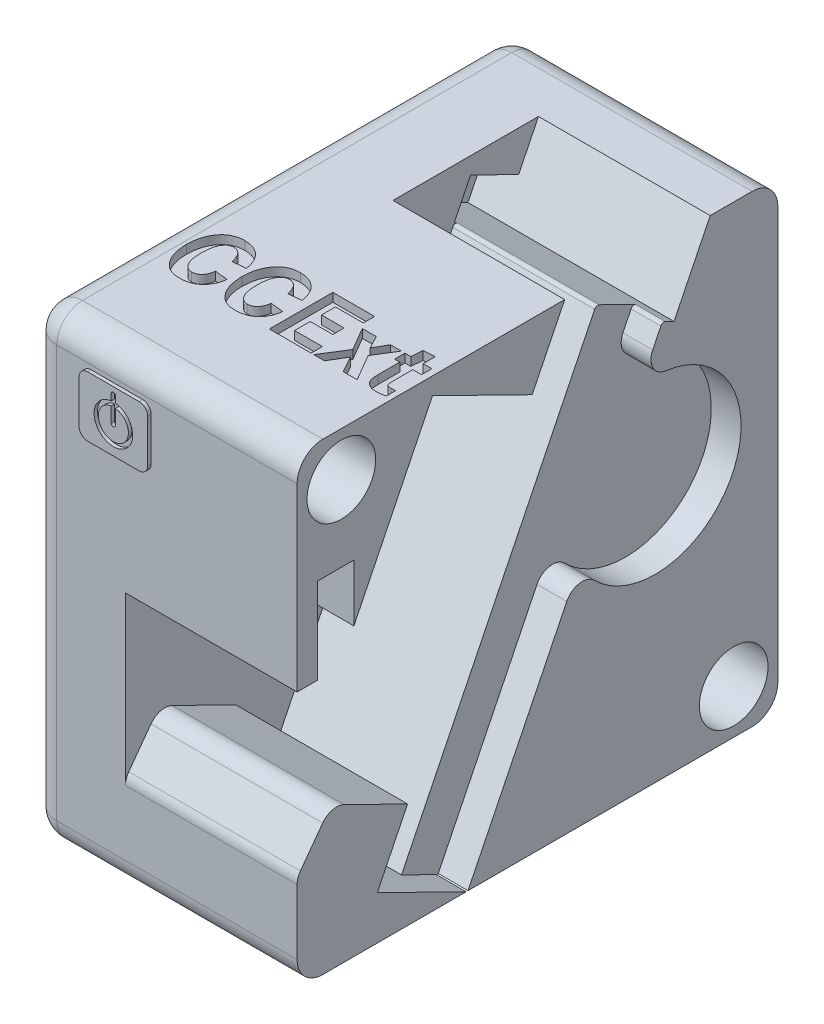
SolidWorks part; units mm, degrees
material "ABS"
ref_plane "Front" through (0, 0, 0) normal (0, 0, 1) x (1, 0, 0)
ref_plane "Top" through (0, 0, 0) normal (0, 1, 0) x (1, 0, 0)
ref_plane "Right" through (0, 0, 0) normal (1, 0, 0) x (0, 0, -1)
sketch "Sketch1" plane through (0, 0, 0) normal (0, 0, 1) x (1, 0, 0)
  line L0 (133.4483, 300.2587) -> (667.2416, 300.2587) construction
  line L2 (-196.85, 342.9) -> (196.85, 342.9)
  line L3 (-196.85, 342.9) -> (-196.85, 0)
  line L4 (-196.85, 0) -> (196.85, 0)
  line L5 (196.85, 342.9) -> (196.85, 0)
  dimension "D1" = 342.9
  dimension "D2" = 393.7
extrude "Boss-Extrude1" add sketch "Sketch1" along normal blind 355.6
sketch "Sketch2" plane through (0, 0, 355.6) normal (0, 0, 1) x (1, 0, 0)
  line L0 (196.85, 342.9) -> (-196.85, 342.9) construction
  line L1 (-158.75, 320.675) -> (-107.95, 320.675)
  line L2 (-158.75, 320.675) -> (-158.75, 276.225)
  line L3 (-158.75, 276.225) -> (-107.95, 276.225)
  line L4 (-107.95, 320.675) -> (-107.95, 276.225)
  line L5 (-158.75, 320.675) -> (-107.95, 276.225) construction
  line L6 (-158.75, 276.225) -> (-107.95, 320.675) construction
  line L7 (-196.85, 342.9) -> (-196.85, 0) construction
  point P0 (-133.35, 298.45)
  dimension "D1" = 44.45
  dimension "D2" = 63.5
  dimension "D3" = 44.45
  dimension "D4" = 50.8
extrude "Boss-Extrude2" add sketch "Sketch2" along normal blind 2.54
sketch "Sketch3" plane through (0, 0, 355.6) normal (0, 0, 1) x (1, 0, 0)
  line L0 (88.9, 298.45) -> (165.1, 298.45) construction
  line L1 (88.9, 307.975) -> (165.1, 307.975)
  line L2 (88.9, 288.925) -> (165.1, 288.925)
  line L5 (-107.95, 298.45) -> (88.9, 298.45) construction
  line L7 (-107.95, 276.225) -> (-107.95, 320.675) construction
  line L8 (196.85, 0) -> (196.85, 342.9) construction
  arc A0 (88.9, 307.975) -> (88.9, 288.925) centre (88.9, 298.45) ccw
  arc A1 (165.1, 288.925) -> (165.1, 307.975) centre (165.1, 298.45) ccw
  point P2 (127, 298.45)
  dimension "D1" = 19.05
  dimension "D2" = 76.2
  dimension "D3" = 31.75
extrude "Boss-Extrude3" add sketch "Sketch3" along normal blind 2.54
sketch "Sketch4" plane through (0, 0, 358.14) normal (0, 0, 1) x (1, 0, 0)
  line L0 (79.375, 298.45) -> (174.625, 298.45) construction
  arc A0 (88.9, 307.975) -> (88.9, 288.925) centre (88.9, 298.45) ccw construction
  arc A1 (165.1, 288.925) -> (165.1, 307.975) centre (165.1, 298.45) ccw construction
  circle A2 centre (92.075, 298.45) radius 3.81
  circle A3 centre (108.2865, 298.45) radius 3.81
  circle A4 centre (124.4979, 298.45) radius 3.81
  dimension "D1" = 7.62
  dimension "D2" = 16.2115
  dimension "D3" = 16.2115
  dimension "D4" = 12.7
extrude "Cut-Extrude1" cut sketch "Sketch4" against normal blind 2.54
sketch "Sketch5" plane through (0, 0, 355.6) normal (0, 0, 1) x (1, 0, 0)
  line L0 (-114.3, 177.8) -> (114.3, 177.8) construction
  line L1 (-114.3, 190.5) -> (114.3, 190.5)
  line L2 (-114.3, 165.1) -> (114.3, 165.1)
  line L3 (0, 177.8) -> (0, 342.9) construction
  line L4 (196.85, 342.9) -> (-196.85, 342.9) construction
  arc A0 (-114.3, 190.5) -> (-114.3, 165.1) centre (-114.3, 177.8) ccw
  arc A1 (114.3, 165.1) -> (114.3, 190.5) centre (114.3, 177.8) ccw
  point P2 (0, 177.8)
  dimension "D1" = 228.6
  dimension "D2" = 25.4
  dimension "D3" = 165.1
extrude "Boss-Extrude4" add sketch "Sketch5" along normal blind 50.8
fillet "Fillet1" radius 6.35 4 edges at (127, 177.8, 406.4) (0, 165.1, 406.4) (-127, 177.8, 406.4) (0, 190.5, 406.4)
fillet "Fillet2" radius 6.35 4 edges at (-158.75, 276.225, 356.87) (-107.95, 276.225, 356.87) (-107.95, 320.675, 356.87) (-158.75, 320.675, 356.87)
sketch "Sketch6" plane through (0, 0, 358.14) normal (0, 0, 1) x (1, 0, 0)
  line L0 (-133.35, 296.545) -> (-133.35, 276.225) construction
  line L3 (-133.35, 296.545) -> (-133.35, 315.595) construction
  line L4 (-134.9375, 296.545) -> (-134.9375, 315.595)
  line L5 (-131.7625, 296.545) -> (-131.7625, 315.595)
  line L6 (-152.4, 276.225) -> (-114.3, 276.225) construction
  circle A1 centre (-133.35, 296.545) radius 11.1125
  circle A2 centre (-133.35, 296.545) radius 14.2875
  arc A3 (-134.9375, 296.545) -> (-131.7625, 296.545) centre (-133.35, 296.545) ccw
  arc A4 (-131.7625, 315.595) -> (-134.9375, 315.595) centre (-133.35, 315.595) ccw
  point P12 (-133.35, 306.07)
  dimension "D2" = 22.225
  dimension "D3" = 3.175
  dimension "D4" = 19.05
  dimension "D5" = 20.32
  dimension "D1" = 3.175
extrude "Cut-Extrude2" cut sketch "Sketch6" against normal blind 2.54 contours L4 A2 L5 A1 | L5 A4 L4 A2 | L5 A2 L4 A1 | L4 A3 L5 A1 region at (-133.35, 301.4538, 358.14) region at (-140.889, 287.8397, 358.14) region at (-133.35, 309.2112, 358.14) region at (-133.35, 313.8328, 358.14)
fillet "Fillet3" radius 19.05 12 edges at (-196.85, 171.45, 0) (-196.85, 171.45, 355.6) (196.85, 171.45, 0) (196.85, 171.45, 355.6) (0, 0, 0) (0, 0, 355.6) (0, 342.9, 0) (0, 342.9, 355.6) (-196.85, 342.9, 177.8) (196.85, 0, 177.8) (-196.85, 0, 177.8) (196.85, 342.9, 177.8)
sketch "Sketch7" plane through (0, 0, 0) normal (1, 0, 0) x (0, 0, -1)
  line L0 (-51.7276, 342.9) -> (10.6627, 469.9)
  line L1 (-336.55, 342.9) -> (-19.05, 342.9) construction
  line L2 (-94.1768, 342.9) -> (-31.7865, 469.9)
  line L3 (-31.7865, 469.9) -> (10.6627, 469.9)
  line L4 (-94.1768, 342.9) -> (-51.7276, 342.9)
  line L5 (0, 323.85) -> (0, 19.05) construction
  dimension "D1" = 38.1
  dimension "D2" = 127
  dimension "D3" = 94.1768
  dimension "D4" = 63.837
extrude "Boss-Extrude5" add sketch "Sketch7" along normal mid plane 254
fillet "Fillet4" radius 39.116 2 edges at (-127, 469.9, 10.5619) (127, 469.9, 10.5619)
sketch "Sketch8" plane through (0, 342.9, 0) normal (0, 1, 0) x (1, 0, 0)
  line L0 (0, -94.1768) -> (0, -125.9268) construction
  line L1 (127, -94.1768) -> (-127, -94.1768) construction
  line L3 (-127, -157.6768) -> (127, -157.6768)
  line L4 (-127, -157.6768) -> (-127, -94.1768)
  line L5 (-127, -94.1768) -> (127, -94.1768)
  line L6 (127, -157.6768) -> (127, -94.1768)
  line L7 (-127, -157.6768) -> (127, -94.1768) construction
  line L8 (-127, -94.1768) -> (127, -157.6768) construction
  dimension "D1" = 63.5
  dimension "D2" = 254
extrude "Cut-Extrude3" cut sketch "Sketch8" against normal blind 25.4
sketch "Sketch9" plane through (0, 0, 0) normal (1, 0, 0) x (0, 0, -1)
  line L1 (-912.7094, 769.4471) -> (-210.006, -1175.153)
  line L2 (-210.006, -1175.153) -> (1122.7154, 405.706)
  line L3 (1122.7154, 405.706) -> (-912.7094, 769.4471)
  circle A0 centre (0, 0) radius 596.8851 construction
extrude "Cut-Extrude4" cut sketch "Sketch9" along normal through all
sketch "Sketch10" plane through (0, 0, 0) normal (1, 0, 0) x (0, 0, -1)
  line L0 (-94.1768, 342.9) -> (-256.3917, 12.7)
  line L1 (-157.6768, 342.9) -> (-181.7103, 293.9781)
  line L2 (-31.7865, 469.9) -> (-94.1768, 342.9) construction
  line L3 (-336.55, 165.1) -> (-255.4426, 330.2)
  line L5 (-355.6, 19.05) -> (-355.6, 165.1) construction
  line L9 (-157.6768, 342.9) -> (-94.1768, 342.9)
  line L14 (-255.4426, 330.2) -> (-181.7103, 293.9781)
  line L15 (-336.55, 0) -> (-19.05, 0) construction
  line L16 (-157.6768, 342.9) -> (-336.55, 342.9) construction
  line L17 (-341.781, 111.2476) -> (-273.8883, 77.8944)
  line L19 (-256.3917, 12.7) -> (-296.2874, 32.2993)
  line L20 (-296.2874, 32.2993) -> (-273.8883, 77.8944)
  line L21 (-336.55, 165.1) -> (-355.6, 165.1)
  line L22 (-355.6, 165.1) -> (-355.6, 83.1181)
  line L23 (-238.3444, 321.8003) -> (-409.5147, -26.6293) construction
  line L24 (-341.781, 111.2476) -> (-355.6, 83.1181)
  dimension "D1" = 12.7
  dimension "D2" = 12.7
  dimension "D3" = 50.8
  dimension "D4" = 44.45
  dimension "D5" = 19.05
  dimension "D6" = 19.05
extrude "Cut-Extrude5" cut sketch "Sketch10" against normal blind 127
sketch "Sketch11" plane through (0, 0, 0) normal (1, 0, 0) x (0, 0, -1)
  line L0 (-94.1768, 342.9) -> (-106.6549, 317.5)
  line L1 (-106.6549, 317.5) -> (-94.1768, 317.5)
  line L2 (-94.1768, 317.5) -> (-94.1768, 342.9)
extrude "Boss-Extrude6" add sketch "Sketch11" against normal up to surface (127 mm away) up to face at (-127, 199.4183, 238.9182)
sketch "Sketch12" plane through (0, 103.9367, 211.5706) normal (0, 0.4409, 0.8975) x (1, 0, 0)
  line L0 (-127, -101.6517) -> (0, -101.6517) construction
  line L1 (0, 426.4566) -> (-22, 426.4566)
  line L2 (0, 426.4566) -> (0, -101.6517)
  line L3 (0, -101.6517) -> (-22, -101.6517)
  line L4 (-22, 426.4566) -> (-22, -101.6517)
  dimension "D1" = 22
extrude "Cut-Extrude6" cut sketch "Sketch12" against normal blind 30
sketch "Sketch13" plane through (0, 0, 0) normal (1, 0, 0) x (0, 0, -1)
  line L0 (-90.7362, 196.8695) -> (0, 196.8695) construction
  line L1 (0, 19.05) -> (0, 323.85) construction
  line L2 (-90.7362, 196.8695) -> (-90.7362, 0) construction
  line L3 (-336.55, 0) -> (-230.5399, 0) construction
  circle A0 centre (-90.7362, 196.8695) radius 63.5
  dimension "D3" = 127
  dimension "D1" = 196.8695
  dimension "D2" = 90.7362
extrude "Cut-Extrude7" cut sketch "Sketch13" against normal up to surface (22 mm away) up to face at (-22, 190.5, 149.2572)
fillet "Fillet5" radius 12.7 2 edges at (-11, 259.4033, 101.771) (-11, 167.3852, 146.9761)
sketch "Sketch14" plane through (0, 0, 0) normal (1, 0, 0) x (0, 0, -1)
  line L0 (-400.05, 165.1) -> (-336.55, 165.1) construction
  line L1 (-255.4426, 330.2) -> (-336.55, 165.1) construction
  line L2 (-255.4426, 330.2) -> (-336.55, 165.1) construction
  line L3 (-355.5357, 165.1) -> (-336.55, 165.1)
  line L4 (-336.55, 165.1) -> (-328.1786, 182.1405)
  arc A0 (-355.5357, 165.1) -> (-328.1786, 182.1405) centre (-355.5357, 195.58) ccw
  dimension "D1" = 30.48
extrude "Cut-Extrude8" cut sketch "Sketch14" against normal up to surface (127 mm away) up to face at (-127, 177.9489, 264.1005)
sketch "Sketch15" plane through (0, 0, 0) normal (1, 0, 0) x (0, 0, -1)
  circle A0 centre (-322.9044, 310.2044) radius 25.4
  circle A1 centre (-32.6956, 32.6956) radius 25.4
  dimension "D1" = 50.8
  dimension "D2" = 50.8
extrude "Cut-Extrude9" cut sketch "Sketch15" against normal blind 53.34
sketch "Sketch16" plane through (0, 342.9, 0) normal (0, 1, 0) x (1, 0, 0)
  line L0 (-177.8, -336.55) -> (-177.8, -285.75) construction
  text T0 "CCExtractor" font "Franklin Gothic Medium" height in points 190
  dimension "D1" = 50.8
extrude "Cut-Extrude10" cut sketch "Sketch16" against normal blind 6.35
fillet "Fillet6" radius 12.7 1 edges at (-63.5, 111.2476, 341.781)
fillet "Fillet7" radius 50.8 1 edges at (-63.5, 83.1181, 355.6)
sketch "Sketch17" plane through (0, 0, 0) normal (1, 0, 0) x (0, 0, -1)
  line L0 (-315.6, 207.7452) -> (-315.6, 254)
  line L1 (-315.6, 254) -> (-340.6, 254)
  line L2 (-340.6, 254) -> (-340.6, 190.5)
  line L3 (-340.6, 190.5) -> (-355.6, 190.5)
  line L8 (-328.1786, 182.1405) -> (-255.4426, 330.2)
  line L9 (-255.4426, 330.2) -> (-181.7103, 293.9781)
  line L10 (-181.7103, 293.9781) -> (-157.6768, 342.9)
  line L11 (-157.6768, 342.9) -> (-336.55, 342.9)
  line L12 (-355.6, 323.85) -> (-355.6, 190.5)
  line L13 (-355.6, 190.5) -> (-400.05, 190.5)
  line L14 (-406.4, 184.15) -> (-406.4, 171.45)
  line L15 (-400.05, 165.1) -> (-355.5357, 165.1)
  line L16 (-328.1786, 182.1405) -> (-315.6, 207.7452)
  line L21 (-355.6, 190.5) -> (-400.05, 190.5)
  line L22 (-406.4, 184.15) -> (-406.4, 171.45)
  line L23 (-400.05, 165.1) -> (-355.5357, 165.1)
  arc A4 (-355.5357, 165.1) -> (-328.1786, 182.1405) centre (-355.5357, 195.58) ccw
  arc A5 (-336.55, 342.9) -> (-355.6, 323.85) centre (-336.55, 323.85) ccw
  arc A6 (-400.05, 190.5) -> (-406.4, 184.15) centre (-400.05, 184.15) ccw
  arc A7 (-406.4, 171.45) -> (-400.05, 165.1) centre (-400.05, 171.45) ccw
  arc A8 (-355.5357, 165.1) -> (-328.1786, 182.1405) centre (-355.5357, 195.58) ccw
  arc A10 (-400.05, 190.5) -> (-406.4, 184.15) centre (-400.05, 184.15) ccw
  arc A11 (-406.4, 171.45) -> (-400.05, 165.1) centre (-400.05, 171.45) ccw
  dimension "D2" = 15
  dimension "D3" = 25
  dimension "D4" = 63.5
  dimension "D1" = 0
extrude "Cut-Extrude11" cut sketch "Sketch17" against normal up to surface (127 mm away) up to face at (-127, 165.4031, 281.3354)
sketch "Sketch18" plane through (-127, 0, 0) normal (1, 0, 0) x (0, 0, -1)
  line L0 (-315.6, 207.7452) -> (-315.6, 254) construction
  line L1 (-340.6, 254) -> (-315.6, 254)
  line L2 (-340.6, 254) -> (-340.6, 234)
  line L3 (-340.6, 234) -> (-315.6, 234)
  line L4 (-315.6, 254) -> (-315.6, 234)
  dimension "D1" = 20
extrude "Cut-Extrude12" cut sketch "Sketch18" against normal blind 25.4
sketch "Sketch19" plane through (0, 0, 0) normal (1, 0, 0) x (0, 0, -1)
  line L0 (-313.6, 211.8164) -> (-315.6, 207.7452)
  line L1 (-255.4426, 330.2) -> (-315.6, 207.7452) construction
  line L2 (-315.6, 207.7452) -> (-315.6, 254)
  line L3 (-315.6, 254) -> (-313.6, 254)
  line L4 (-313.6, 254) -> (-313.6, 211.8164)
  dimension "D1" = 2
extrude "Cut-Extrude13" cut sketch "Sketch19" against normal up to surface (127 mm away) up to face at (-127, 178.9975, 285.6136)
sketch "Sketch20" plane through (-127, 0, 0) normal (1, 0, 0) x (0, 0, -1)
  line L0 (-313.6, 211.8164) -> (-313.6, 254) construction
  line L1 (-313.6, 232) -> (-340.6, 232)
  line L2 (-313.6, 232) -> (-313.6, 254)
  line L3 (-313.6, 254) -> (-340.6, 254)
  line L4 (-340.6, 232) -> (-340.6, 254)
  line L5 (-340.6, 234) -> (-315.6, 234) construction
  dimension "D1" = 2
extrude "Cut-Extrude14" cut sketch "Sketch20" against normal blind 25.4
sketch "Sketch21" plane through (0, 0, 0) normal (1, 0, 0) x (0, 0, -1)
  line L0 (-94.1768, 342.9) -> (-112.3576, 305.8917)
  line L1 (-256.3917, 12.7) -> (-94.1768, 342.9) construction
  line L2 (-112.3576, 305.8917) -> (-85.4314, 292.6639)
  line L3 (1.6381, 469.9) -> (-92.6006, 278.0704) construction
  line L4 (-85.4314, 292.6639) -> (-78.1613, 289.0923)
  line L5 (-78.1613, 289.0923) -> (-51.7276, 342.9)
  line L6 (-51.7276, 342.9) -> (10.6627, 469.9) construction
  line L7 (-19.05, 342.9) -> (-51.7276, 342.9) construction
  line L8 (-94.1768, 342.9) -> (-31.7865, 469.9)
  line L9 (-31.7865, 469.9) -> (10.6627, 469.9)
  line L10 (10.6627, 469.9) -> (-51.7276, 342.9)
extrude "Cut-Extrude16" cut sketch "Sketch21" against normal up to surface (127 mm away) up to face at (-127, 179.0019, 285.3636)
sketch "Sketch22" plane through (-127, 0, 0) normal (1, 0, 0) x (0, 0, -1)
  line L0 (-78.1613, 289.0923) -> (-112.3576, 305.8917)
  line L1 (-78.1613, 289.0923) -> (-66.0798, 313.685)
  line L2 (-112.3576, 305.8917) -> (-100.2762, 330.4844)
  line L3 (-66.0798, 313.685) -> (-100.2762, 330.4844)
  dimension "D1" = 27.4
extrude "Cut-Extrude17" cut sketch "Sketch22" against normal blind 25.4
sketch "Sketch23" plane through (0, 0, 0) normal (1, 0, 0) x (0, 0, -1)
  line L0 (-78.1613, 289.0923) -> (-76.815, 288.4309)
  line L1 (-76.815, 288.4309) -> (-50.0564, 342.9)
  line L2 (-19.05, 342.9) -> (-51.7276, 342.9) construction
  line L3 (-50.0564, 342.9) -> (-51.7276, 342.9)
  line L4 (-51.7276, 342.9) -> (-78.1613, 289.0923)
  line L5 (-112.3576, 305.8917) -> (-78.1613, 289.0923) construction
  dimension "D1" = 1.5
extrude "Cut-Extrude18" cut sketch "Sketch23" against normal up to surface (127 mm away) up to face at (-127, 200.7417, 252.7411)
sketch "Sketch24" plane through (-127, 0, 0) normal (1, 0, 0) x (0, 0, -1)
  line L0 (-78.1613, 289.0923) -> (-76.815, 288.4309)
  line L1 (-78.1613, 289.0923) -> (-66.0798, 313.685)
  line L2 (-76.815, 288.4309) -> (-64.7335, 313.0236)
  line L3 (-66.0798, 313.685) -> (-64.7335, 313.0236)
extrude "Cut-Extrude19" cut sketch "Sketch24" against normal up to surface (25.4 mm away) up to face at (-152.4, 309.7884, 89.2187)
fillet "Fillet8" radius 2.54 1 edges at (-11, 292.6639, 85.4314)
fillet "Fillet9" radius 2.54 1 edges at (-74.5, 305.8917, 112.3576)
sketch "Sketch25" plane through (0, 0, 0) normal (1, 0, 0) x (0, 0, -1)
  line L0 (-330.3822, 105.6478) -> (-355.6, 71.3138)
  line L10 (-347.3808, 99.8488) -> (-350.3951, 93.713)
  line L11 (-347.3808, 99.8488) -> (-350.3951, 93.713)
  arc A9 (-350.3951, 93.713) -> (-355.6, 71.3138) centre (-304.8, 71.3138) ccw
  arc A10 (-330.3822, 105.6478) -> (-347.3808, 99.8488) centre (-335.982, 94.249) ccw
  arc A11 (-350.3951, 93.713) -> (-355.6, 71.3138) centre (-304.8, 71.3138) ccw
  arc A12 (-330.3822, 105.6478) -> (-347.3808, 99.8488) centre (-335.982, 94.249) ccw
  dimension "D1" = 0
extrude "Cut-Extrude20" cut sketch "Sketch25" against normal up to surface (127 mm away) up to face at (-127, 210.5961, 239.1838)
fillet "Fillet10" radius 12.7 2 edges at (-63.5, 71.3138, 355.6) (-63.5, 105.6478, 330.3822)
equation "\"D3@Sketch4\"=\"D2@Sketch4\""
